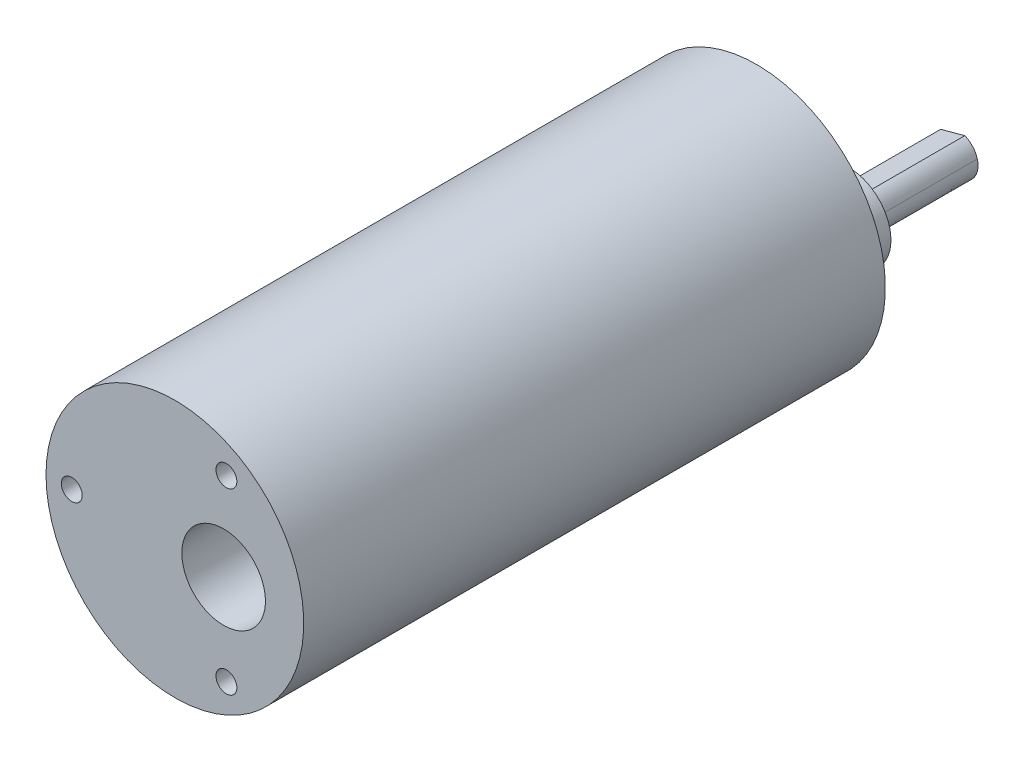
SolidWorks part; units mm, degrees
note: The reader was unsure of these and kept them because the rebuilt part matched: shared geometry of "Sketch1<4>", "Sketch1<5>".
ref_plane "Front Plane" through (0, 0, 0) normal (0, 0, 1) x (1, 0, 0)
ref_plane "Top Plane" through (0, 0, 0) normal (0, 1, 0) x (1, 0, 0)
ref_plane "Right Plane" through (0, 0, 0) normal (1, 0, 0) x (0, 0, -1)
sketch "Sketch1" plane through (0, 0, 0) normal (0, 0, 1) x (1, 0, 0)
  line L0 (8.1054, 2.7889) -> (4.6322, 1.8421)
  arc A0 (1, 0) -> (13, 0) centre (7, 0) ccw
  arc A1 (13, 0) -> (1, 0) centre (7, 0) ccw
  arc A4 (18.5, 0) -> (-18.5, 0) centre (0, 0) ccw
  arc A5 (-18.5, 0) -> (18.5, 0) centre (0, 0) ccw
  circle A6 centre (7.4004, 12.8178) radius 1.5
  circle A7 centre (-14.8007, 0) radius 1.5
  circle A8 centre (7.4004, -12.8178) radius 1.5
  spline S0 degree 3 poles (4.6322, 1.8421) (4.5973, 1.7957) (4.5276, 1.703) (4.4336, 1.5567) (4.3477, 1.4056) (4.2452, 1.1976) (4.1396, 0.9271) (4.0518, 0.59) (4.003, 0.2451) (3.9956, -0.103) (4.0253, -0.4505) (4.0788, -0.6762) (4.1056, -0.789) knots 0 0 0 0 0.062622 0.125035 0.18745 0.250079 0.375057 0.500053 0.62503 0.750026 0.875009 1 1 1 1
  spline S1 degree 3 poles (4.1056, -0.789) (4.1213, -0.8433) (4.1527, -0.9516) (4.2108, -1.1098) (4.2769, -1.264) (4.3517, -1.4139) (4.4349, -1.5595) (4.5267, -1.7009) (4.709, -1.9501) (5.0184, -2.2796) (5.5019, -2.6208) (6.0415, -2.8643) (6.6189, -2.9946) (7.2106, -3.0131) (7.7939, -2.9125) (8.3476, -2.7031) (8.8481, -2.387) (9.2795, -1.9817) (9.6209, -1.498) (9.8644, -0.9586) (9.973, -0.4765) (10.0041, -0.0848) (9.9978, 0.2095) (9.9642, 0.5022) (9.9177, 0.6931) (9.8944, 0.789) knots 0 0 0 0 0.018019 0.035897 0.053689 0.071452 0.089244 0.107123 0.125143 0.187619 0.250101 0.312577 0.375059 0.437535 0.500017 0.562493 0.624975 0.687451 0.749933 0.812409 0.874891 0.90632 0.937444 0.968569 1 1 1 1
  spline S2 degree 3 poles (9.8944, 0.789) (9.8782, 0.8448) (9.8459, 0.9561) (9.7852, 1.1191) (9.7159, 1.2785) (9.611, 1.4852) (9.4579, 1.7321) (9.2409, 2.0045) (8.9942, 2.2505) (8.7203, 2.4653) (8.4245, 2.6501) (8.2118, 2.7426) (8.1054, 2.7889) knots 0 0 0 0 0.062622 0.125035 0.18745 0.250079 0.375057 0.500053 0.62503 0.750026 0.875009 1 1 1 1
  spline S3 degree 3 poles (8.1054, 2.7889) (8.055, 2.808) (7.9545, 2.8461) (7.8004, 2.8928) (7.6447, 2.9317) (7.487, 2.9619) (7.3275, 2.9836) (7.0603, 3.0056) (6.6833, 2.9968) (6.2077, 2.9066) (5.7521, 2.7429) (5.3758, 2.5331) (5.0751, 2.3084) (4.8375, 2.0901) (4.7007, 1.9249) (4.6322, 1.8421) knots 0 0 0 0 0.041904 0.083566 0.125104 0.166642 0.208299 0.250195 0.375078 0.500045 0.624999 0.749895 0.833413 0.916458 1 1 1 1
  point P0 (7.4004, -12.8178)
  point P1 (7.4004, 12.8178)
  point P2 (-14.8007, 0)
  dimension "D1" = 3
extrude "Boss-Extrude1" add sketch "Sketch1" along normal blind 83.5
extrude "Boss-Extrude2" add sketch "Sketch1<4>" against normal blind 6.3 separate body contours A0 A1 S3 S2 S1 S0
sketch "Sketch1<4>" plane through (0, 0, 0) normal (0, 0, 1) x (1, 0, 0) same geometry as "Sketch1"
extrude "Boss-Extrude3" add sketch "Sketch1<5>" against normal blind 21.8 contours S2 L0 S0 S1
sketch "Sketch1<5>" plane through (0, 0, 0) normal (0, 0, 1) x (1, 0, 0) same geometry as "Sketch1"
